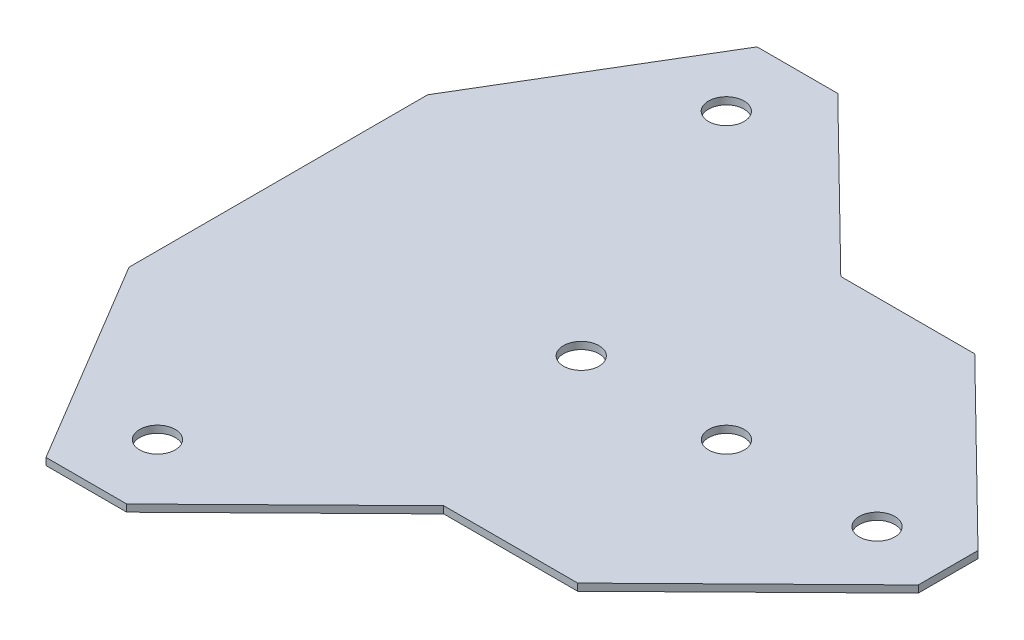
SolidWorks part; units mm, degrees
material "ABS"
ref_plane "Front Plane" through (0, 0, 0) normal (0, 0, 1) x (1, 0, 0)
ref_plane "Top Plane" through (0, 0, 0) normal (0, 1, 0) x (1, 0, 0)
ref_plane "Right Plane" through (0, 0, 0) normal (1, 0, 0) x (0, 0, -1)
sketch "Sketch1" plane through (0, 0, 0) normal (0, 1, 0) x (1, 0, 0)
  line L0 (5.6744, 50) -> (28.1809, 27.92)
  line L5 (28.1809, 27.92) -> (47.02, 27.92)
  line L6 (47.02, 27.92) -> (71.2, 4.1983)
  line L11 (47.02, -27.92) -> (71.2, -4.1983)
  line L12 (28.1809, -27.92) -> (47.02, -27.92)
  line L13 (5.6744, -50) -> (28.1809, -27.92)
  line L14 (-23, 21) -> (-23, -21)
  line L27 (-23, 21) -> (-5.6744, 50)
  line L38 (-5.6744, 50) -> (5.6744, 50)
  line L40 (71.2, 4.1983) -> (71.2, -4.1983)
  line L41 (-23, 0) -> (71.2, 0) construction
  line L43 (-23, -21) -> (-5.6744, -50)
  line L45 (-5.6744, -50) -> (5.6744, -50)
  line L55 (0, 40) -> (0, 0) construction
  line L56 (0, 0) -> (61.2, 0) construction
  line L57 (12.6, -5.5) -> (47.02, -5.5) construction
  line L58 (47.02, -5.5) -> (47.02, 27.92) construction
  line L59 (47.02, 27.92) -> (12.6, 27.92) construction
  line L60 (12.6, 27.92) -> (12.6, 19.52) construction
  line L61 (12.6, 19.52) -> (42.6, 19.52) construction
  line L62 (42.6, 19.52) -> (42.6, 14.52) construction
  line L63 (42.6, 14.52) -> (12.6, 14.52) construction
  line L64 (12.6, 14.52) -> (12.6, -5.5) construction
  line L65 (29.81, -5.5) -> (29.81, 14.52) construction
  circle A26 centre (0, 40) radius 2.5
  circle A27 centre (0, -40) radius 2.5
  circle A28 centre (61.2, 0) radius 2.5
  circle A31 centre (19.6, 0) radius 2.5
  circle A32 centre (40.02, 0) radius 2.5
  point P3 (0, 50)
  point P4 (-23, 0)
  point P5 (-23, -19.574)
  point P120 (30.6, 0)
  dimension "D5" = 42
  dimension "D7" = 5
  dimension "D8" = 61.2
  dimension "D10" = 23
  dimension "D11" = 40
  dimension "D23" = 10
  dimension "D24" = 5
  dimension "D25" = 10
  dimension "D26" = 10
  dimension "D9" = 10
  dimension "D36" = 34.42
  dimension "D37" = 8.4
  dimension "D38" = 30
  dimension "D39" = 33.42
  dimension "D40" = 5
  dimension "D41" = 5.5
  dimension "D42" = 7
  dimension "D43" = 18
base flange "Base-Flange1" sketch "Sketch1" thickness 1 reverse thickness direction no parameters "D1"=0.7366
sketch "Bend-Lines1" [suppressed] plane through (0, 0, 0) normal (0, 1, 0) x (1, 0, 0)
sketch "Bounding-Box1" [suppressed] plane through (0, 0, 0) normal (0, 1, 0) x (1, 0, 0)
sheet metal parameters "Sheet-Metal12" thickness 1 parameters "D1"=0.7366
flat pattern "Flat-Pattern12" [suppressed]
sketch "Bend-Lines2" plane through (0, 0, 0) normal (0, 1, 0) x (1, 0, 0)
sketch3d "Bounding-Box2" [suppressed]
  line L0 (75.3975, 0.0803, 0) -> (9.1307, 65.0911, 0) construction
  line L1 (10.6016, -65.9675, 0) -> (-55.6652, -0.9566, 0) construction
  line L2 (75.3975, 0.0803, 0) -> (10.6016, -65.9675, 0) construction
  line L3 (9.1307, 65.0911, 0) -> (-55.6652, -0.9566, 0) construction
